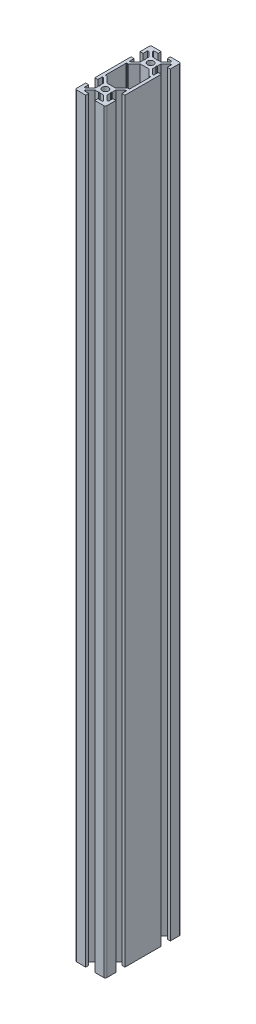
SolidWorks part; units mm, degrees
material "6063-T5"
ref_plane "Top Plane" through (0, 0, 0) normal (0, 0, 1) x (1, 0, 0)
ref_plane "Front Plane" through (0, 0, 0) normal (0, 1, 0) x (1, 0, 0)
ref_plane "Side Plane" through (0, 0, 0) normal (1, 0, 0) x (0, 0, -1)
sketch "Sketch3" plane through (0, 0, 0) normal (0, 1, 0) x (1, 0, 0)
  line L0 (-6.9602, 12.0172) -> (-7.5966, 12.0172)
  line L1 (-7.8966, 11.7172) -> (-7.8966, -1.6828)
  line L2 (-7.5966, -1.9828) -> (-6.9602, -1.9828)
  line L3 (-6.7481, -2.0706) -> (-2.836, -5.9828)
  line L4 (-2.836, -5.9828) -> (3.0427, -5.9828)
  line L5 (3.0427, -5.9828) -> (6.9548, -2.0706)
  line L6 (7.167, -1.9828) -> (7.8034, -1.9828)
  line L7 (8.1034, -1.6828) -> (8.1034, 11.7172)
  line L8 (7.8034, 12.0172) -> (7.167, 12.0172)
  line L9 (6.9548, 12.1051) -> (3.0427, 16.0172)
  line L10 (-2.836, 16.0172) -> (-6.7481, 12.1051)
  line L11 (3.0427, 16.0172) -> (-2.836, 16.0172)
  line L12 (-9.8966, 17.0172) -> (-9.8966, -6.9828)
  line L13 (-9.8966, -6.9828) -> (-7.8966, -6.9828)
  line L14 (-7.8966, -6.9828) -> (-7.8966, -3.9828)
  line L15 (-7.8966, -3.9828) -> (-6.9573, -3.9828)
  line L16 (-6.9573, -3.9828) -> (-3.8966, -7.0434)
  line L17 (-3.8966, -7.0434) -> (-3.8966, -7.4828)
  line L18 (-3.8966, -7.4828) -> (-3.8966, -9.3292)
  line L20 (-3.8297, -9.5792) -> (-3.5966, -9.9828)
  line L21 (-3.5966, -9.9828) -> (-3.8297, -10.3864)
  line L22 (-3.8966, -10.6364) -> (-3.8966, -12.9221)
  line L23 (-3.8966, -12.9221) -> (-6.9573, -15.9828)
  line L24 (-6.9573, -15.9828) -> (-7.8966, -15.9828)
  line L25 (-7.8966, -15.9828) -> (-7.8966, -12.9828)
  line L26 (-7.8966, -12.9828) -> (-9.8966, -12.9828)
  line L27 (-9.8966, -12.9828) -> (-9.8966, -18.9828)
  line L28 (-8.8966, -19.9828) -> (-2.8966, -19.9828)
  line L29 (-2.8966, -19.9828) -> (-2.8966, -17.9828)
  line L30 (-2.8966, -17.9828) -> (-5.8966, -17.9828)
  line L31 (-5.8966, -17.9828) -> (-5.8966, -17.0434)
  line L32 (-5.8966, -17.0434) -> (-2.836, -13.9828)
  line L33 (-2.836, -13.9828) -> (-2.3966, -13.9828)
  line L34 (-2.3966, -13.9828) -> (-0.5502, -13.9828)
  line L36 (-0.3002, -13.9158) -> (0.1034, -13.6828)
  line L37 (0.1034, -13.6828) -> (0.5069, -13.9158)
  line L38 (0.7569, -13.9828) -> (3.0427, -13.9828)
  line L39 (3.0427, -13.9828) -> (6.1034, -17.0434)
  line L40 (6.1034, -17.0434) -> (6.1034, -17.9828)
  line L41 (6.1034, -17.9828) -> (3.1034, -17.9828)
  line L42 (3.1034, -17.9828) -> (3.1034, -19.9828)
  line L43 (3.1034, -19.9828) -> (9.1034, -19.9828)
  line L44 (10.1034, -18.9828) -> (10.1034, -12.9828)
  line L45 (10.1034, -12.9828) -> (8.1034, -12.9828)
  line L46 (8.1034, -12.9828) -> (8.1034, -15.9828)
  line L47 (8.1034, -15.9828) -> (7.164, -15.9828)
  line L48 (7.164, -15.9828) -> (4.1034, -12.9221)
  line L49 (4.1034, -12.9221) -> (4.1034, -12.4828)
  line L50 (4.1034, -12.4828) -> (4.1034, -10.6364)
  line L52 (4.0364, -10.3864) -> (3.8034, -9.9828)
  line L53 (3.8034, -9.9828) -> (4.0364, -9.5792)
  line L54 (4.1034, -9.3292) -> (4.1034, -7.0434)
  line L55 (4.1034, -7.0434) -> (7.164, -3.9828)
  line L56 (7.164, -3.9828) -> (8.1034, -3.9828)
  line L57 (8.1034, -3.9828) -> (8.1034, -6.9828)
  line L58 (8.1034, -6.9828) -> (10.1034, -6.9828)
  line L59 (10.1034, -6.9828) -> (10.1034, 17.0172)
  line L60 (10.1034, 17.0172) -> (8.1034, 17.0172)
  line L61 (8.1034, 17.0172) -> (8.1034, 14.0172)
  line L62 (8.1034, 14.0172) -> (7.164, 14.0172)
  line L63 (7.164, 14.0172) -> (4.1034, 17.0779)
  line L64 (4.1034, 17.0779) -> (4.1034, 19.3636)
  line L65 (4.0364, 19.6136) -> (3.8034, 20.0172)
  line L66 (3.8034, 20.0172) -> (4.0364, 20.4208)
  line L68 (4.1034, 20.6708) -> (4.1034, 22.5172)
  line L69 (4.1034, 22.5172) -> (4.1034, 22.9566)
  line L70 (4.1034, 22.9566) -> (7.164, 26.0172)
  line L71 (7.164, 26.0172) -> (8.1034, 26.0172)
  line L72 (8.1034, 26.0172) -> (8.1034, 23.0172)
  line L73 (8.1034, 23.0172) -> (10.1034, 23.0172)
  line L74 (10.1034, 23.0172) -> (10.1034, 29.0172)
  line L75 (9.1034, 30.0172) -> (3.1034, 30.0172)
  line L76 (3.1034, 30.0172) -> (3.1034, 28.0172)
  line L77 (3.1034, 28.0172) -> (6.1034, 28.0172)
  line L78 (6.1034, 28.0172) -> (6.1034, 27.0779)
  line L79 (6.1034, 27.0779) -> (3.0427, 24.0172)
  line L80 (3.0427, 24.0172) -> (0.7569, 24.0172)
  line L81 (0.5069, 23.9502) -> (0.1034, 23.7172)
  line L82 (0.1034, 23.7172) -> (-0.3002, 23.9502)
  line L84 (-0.5502, 24.0172) -> (-2.3966, 24.0172)
  line L85 (-2.3966, 24.0172) -> (-2.836, 24.0172)
  line L86 (-2.836, 24.0172) -> (-5.8966, 27.0779)
  line L87 (-5.8966, 27.0779) -> (-5.8966, 28.0172)
  line L88 (-5.8966, 28.0172) -> (-2.8966, 28.0172)
  line L89 (-2.8966, 28.0172) -> (-2.8966, 30.0172)
  line L90 (-2.8966, 30.0172) -> (-8.8966, 30.0172)
  line L91 (-9.8966, 29.0172) -> (-9.8966, 23.0172)
  line L92 (-9.8966, 23.0172) -> (-7.8966, 23.0172)
  line L93 (-7.8966, 23.0172) -> (-7.8966, 26.0172)
  line L94 (-7.8966, 26.0172) -> (-6.9573, 26.0172)
  line L95 (-6.9573, 26.0172) -> (-3.8966, 22.9566)
  line L96 (-3.8966, 22.9566) -> (-3.8966, 20.6708)
  line L97 (-3.8297, 20.4208) -> (-3.5966, 20.0172)
  line L98 (-3.5966, 20.0172) -> (-3.8297, 19.6136)
  line L100 (-3.8966, 19.3636) -> (-3.8966, 17.5172)
  line L101 (-3.8966, 17.5172) -> (-3.8966, 17.0779)
  line L102 (-3.8966, 17.0779) -> (-6.9573, 14.0172)
  line L103 (-6.9573, 14.0172) -> (-7.8966, 14.0172)
  line L104 (-7.8966, 14.0172) -> (-7.8966, 17.0172)
  line L105 (-7.8966, 17.0172) -> (-9.8966, 17.0172)
  arc A0 (-1.9966, -9.9828) -> (2.2034, -9.9828) centre (0.1034, -9.9828) ccw
  arc A1 (2.2034, -9.9828) -> (-1.9966, -9.9828) centre (0.1034, -9.9828) ccw
  arc A2 (-7.5966, 12.0172) -> (-7.8966, 11.7172) centre (-7.5966, 11.7172) ccw
  arc A3 (-6.9602, 12.0172) -> (-6.7481, 12.1051) centre (-6.9602, 12.3172) ccw
  arc A4 (-3.8966, -9.3292) -> (-3.8297, -9.5792) centre (-3.3966, -9.3292) ccw
  arc A5 (-3.8297, -10.3864) -> (-3.8966, -10.6364) centre (-3.3966, -10.6364) ccw
  arc A6 (-9.8966, -18.9828) -> (-8.8966, -19.9828) centre (-8.8966, -18.9828) ccw
  arc A7 (-0.5502, -13.9828) -> (-0.3002, -13.9158) centre (-0.5502, -13.4828) ccw
  arc A8 (0.5069, -13.9158) -> (0.7569, -13.9828) centre (0.7569, -13.4828) ccw
  arc A9 (9.1034, -19.9828) -> (10.1034, -18.9828) centre (9.1034, -18.9828) ccw
  arc A10 (4.1034, -10.6364) -> (4.0364, -10.3864) centre (3.6034, -10.6364) ccw
  arc A11 (4.0364, -9.5792) -> (4.1034, -9.3292) centre (3.6034, -9.3292) ccw
  arc A12 (4.1034, 19.3636) -> (4.0364, 19.6136) centre (3.6034, 19.3636) ccw
  arc A13 (4.0364, 20.4208) -> (4.1034, 20.6708) centre (3.6034, 20.6708) ccw
  arc A14 (10.1034, 29.0172) -> (9.1034, 30.0172) centre (9.1034, 29.0172) ccw
  arc A15 (0.7569, 24.0172) -> (0.5069, 23.9502) centre (0.7569, 23.5172) ccw
  arc A16 (-0.3002, 23.9502) -> (-0.5502, 24.0172) centre (-0.5502, 23.5172) ccw
  arc A17 (-8.8966, 30.0172) -> (-9.8966, 29.0172) centre (-8.8966, 29.0172) ccw
  arc A18 (-3.8966, 20.6708) -> (-3.8297, 20.4208) centre (-3.3966, 20.6708) ccw
  arc A19 (-3.8297, 19.6136) -> (-3.8966, 19.3636) centre (-3.3966, 19.3636) ccw
  arc A20 (-7.8966, -1.6828) -> (-7.5966, -1.9828) centre (-7.5966, -1.6828) ccw
  arc A21 (-6.7481, -2.0706) -> (-6.9602, -1.9828) centre (-6.9602, -2.2828) ccw
  arc A22 (7.167, -1.9828) -> (6.9548, -2.0706) centre (7.167, -2.2828) ccw
  arc A23 (7.8034, -1.9828) -> (8.1034, -1.6828) centre (7.8034, -1.6828) ccw
  arc A24 (8.1034, 11.7172) -> (7.8034, 12.0172) centre (7.8034, 11.7172) ccw
  arc A25 (6.9548, 12.1051) -> (7.167, 12.0172) centre (7.167, 12.3172) ccw
  arc A26 (-1.9966, 20.0172) -> (2.2034, 20.0172) centre (0.1034, 20.0172) ccw
  arc A27 (2.2034, 20.0172) -> (-1.9966, 20.0172) centre (0.1034, 20.0172) ccw
  point P15 (0, 0)
  point P52 (0, 0)
  point P84 (0, 0)
  point P117 (0, 0)
  point P136 (0, 0)
  point P155 (0, 0)
  point P162 (0, 0)
  point P163 (0, 0)
  point P164 (0, 0)
  point P165 (0, 0)
  point P166 (0, 0)
  point P167 (0, 0)
  point P168 (0, 0)
  point P169 (0, 0)
  point P170 (0, 0)
  point P171 (0, 0)
  point P172 (0, 0)
  point P173 (0, 0)
  point P174 (0, 0)
  point P175 (0, 0)
extrude "Boss-Extrude3" add sketch "Sketch3" along normal blind 500
